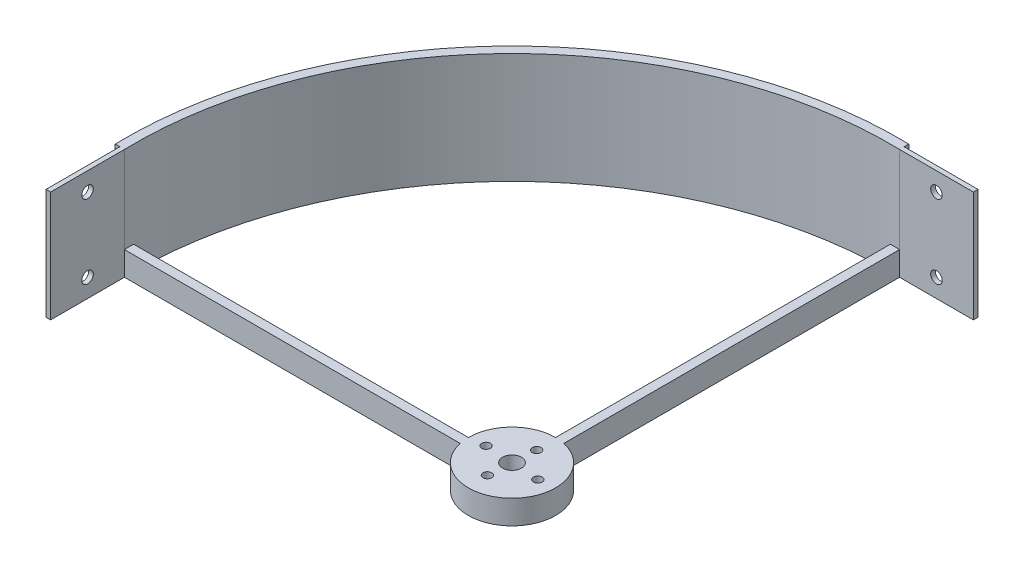
SolidWorks part; units mm, degrees
material "ABS"
ref_plane "Front Plane" through (0, 0, 0) normal (0, 0, 1) x (1, 0, 0)
ref_plane "Top Plane" through (0, 0, 0) normal (0, 1, 0) x (1, 0, 0)
ref_plane "Right Plane" through (0, 0, 0) normal (1, 0, 0) x (0, 0, -1)
sketch "Sketch1" plane through (0, 0, 0) normal (0, 1, 0) x (1, 0, 0)
  line L0 (0, 130.175) -> (0, 9.3426)
  line L1 (3.175, 9.3426) -> (3.175, 130.1363)
  line L2 (0, 0) -> (-22.0351, 22.0351) construction
  line L3 (-22.0351, 22.0351) -> (23.6345, -23.6345) construction
  line L4 (-9.3426, -3.175) -> (-130.1363, -3.175)
  line L5 (-130.175, 0) -> (-9.3426, 0)
  line L6 (3.175, 9.3426) -> (3.175, 130.1363)
  line L7 (3.175, 130.1363) -> (3.175, 133.3122)
  line L8 (-130.1363, -3.175) -> (-133.3122, -3.175)
  circle A0 centre (0, 0) radius 15
  arc A1 (3.175, 130.1363) -> (-130.1363, -3.175) centre (0, 0) ccw
  arc A2 (3.175, 133.3122) -> (-133.3122, -3.175) centre (0, 0) ccw
  dimension "D1" = 30
  dimension "D2" = 133.35
  dimension "D4" = 3.175
  dimension "D3" = 3.175
extrude "Boss-Extrude2" add sketch "Sketch1" along normal blind 8.255 contours A0
extrude "Boss-Extrude3" add sketch "Sketch1<6>" along normal blind 8.255 contours L5 A1 L4 A0 | L6 A1 L0 A0 region at (1.5882, 0, -72.5246) region at (-72.5246, 0, 1.5882)
sketch "Sketch1<6>" plane through (0, 0, 0) normal (0, 1, 0) x (1, 0, 0) same geometry as "Sketch1"
extrude "Boss-Extrude4" add sketch "Sketch1<7>" along normal blind 38.1 contours L7 A2 L8 A1 region at (-93.4129, 0, -93.4129)
sketch "Sketch1<7>" plane through (0, 0, 0) normal (0, 1, 0) x (1, 0, 0) same geometry as "Sketch1"
ref_plane "Plane1" through (-63.4806, 0, -63.4806) normal (0.7071, 0, 0.7071) x (0.7071, 0, -0.7071)
sketch "Sketch5" plane through (0, 8.255, 0) normal (0, 1, 0) x (1, 0, 0)
  line L0 (0, 0) -> (29.635, 0) construction
  line L1 (0, 0) -> (0, 21.5427) construction
  line L2 (0, 130.175) -> (0, 15) construction
  line L3 (0, 0) -> (29.1655, -1.7838) construction
  line L4 (21.3209, -1.304) -> (-27.7157, 1.6952) construction
  line L5 (0, 0) -> (1.3244, 21.6543) construction
  line L6 (0, 8) -> (0, 0) construction
  line L7 (0, 0) -> (37.8993, -60.1598) construction
  line L8 (0, 0) -> (-19.6346, 0) construction
  line L9 (-130.175, 0) -> (-15, 0) construction
  circle A0 centre (-9.4823, 0.58) radius 1.5
  circle A1 centre (0.4884, 7.9851) radius 1.5
  circle A2 centre (-0.4884, -7.9851) radius 1.5
  circle A3 centre (9.4823, -0.58) radius 1.5
  circle A6 centre (0, 0) radius 3.25
  point P18 (0, 0)
  dimension "D3" = 3
  dimension "D7" = 3
  dimension "D8" = 6.5
  dimension "D2" = 8
  dimension "D5" = 93.5
  dimension "D6" = 8
  dimension "D9" = 90
  dimension "D10" = 9.5
  dimension "D4" = 57.79
extrude "Cut-Extrude3" cut sketch "Sketch5" against normal blind 63.5
sketch "Sketch6" plane through (0, 0, 3.175) normal (0, 0, 1) x (1, 0, 0)
  line L0 (-14.6601, 0) -> (-133.3122, 0) construction
  line L1 (-130.1363, 38.1) -> (-131.7242, 38.1)
  line L2 (-130.1363, 38.1) -> (-130.1363, 0)
  line L3 (-130.1363, 0) -> (-131.7242, 0)
  line L4 (-131.7242, 38.1) -> (-131.7242, 0)
  line L5 (-130.1363, 38.1) -> (-133.3122, 38.1) construction
  point P7 (-131.7242, 38.1)
extrude "Boss-Extrude5" add sketch "Sketch6" along normal blind 25.4
sketch "Sketch7" plane through (3.175, 0, 0) normal (1, 0, 0) x (0, 0, -1)
  line L0 (14.6601, 0) -> (133.3122, 0) construction
  line L1 (130.1363, 38.1) -> (131.7242, 38.1)
  line L2 (130.1363, 38.1) -> (130.1363, 0)
  line L3 (130.1363, 0) -> (131.7242, 0)
  line L4 (131.7242, 38.1) -> (131.7242, 0)
  line L5 (130.1363, 38.1) -> (133.3122, 38.1) construction
  line L6 (130.1363, 38.1) -> (130.1363, 8.255) construction
  point P7 (131.7242, 38.1)
extrude "Boss-Extrude6" add sketch "Sketch7" along normal blind 25.4
sketch "Sketch8" plane through (-131.7242, 0, 0) normal (-1, 0, 0) x (0, 0, 1)
  line L0 (3.175, 19.05) -> (28.575, 19.05) construction
  line L1 (3.175, 38.1) -> (3.175, 0) construction
  line L2 (28.575, 38.1) -> (28.575, 0) construction
  line L3 (15.875, 19.05) -> (15.875, 31.75) construction
  circle A0 centre (15.875, 31.75) radius 1.9844
  circle A1 centre (15.875, 6.35) radius 1.9844
  dimension "D1" = 3.9688
  dimension "D2" = 12.7
extrude "Cut-Extrude4" cut sketch "Sketch8" against normal up to surface (1.588 mm away) up to face at (-130.1363, 16.891, 13.335)
sketch "Sketch9" plane through (0, 0, -131.7242) normal (0, 0, -1) x (-1, 0, 0)
  line L0 (-28.575, 19.05) -> (-3.175, 19.05) construction
  line L1 (-28.575, 0) -> (-28.575, 38.1) construction
  line L2 (-3.175, 0) -> (-3.175, 38.1) construction
  line L3 (-15.875, 19.05) -> (-15.875, 31.75) construction
  circle A0 centre (-15.875, 31.75) radius 1.9844
  circle A1 centre (-15.875, 6.35) radius 1.9844
  dimension "D1" = 3.9688
  dimension "D2" = 12.7
extrude "Cut-Extrude5" cut sketch "Sketch9" against normal up to surface (1.588 mm away) up to face at (13.335, 16.891, -130.1363)
